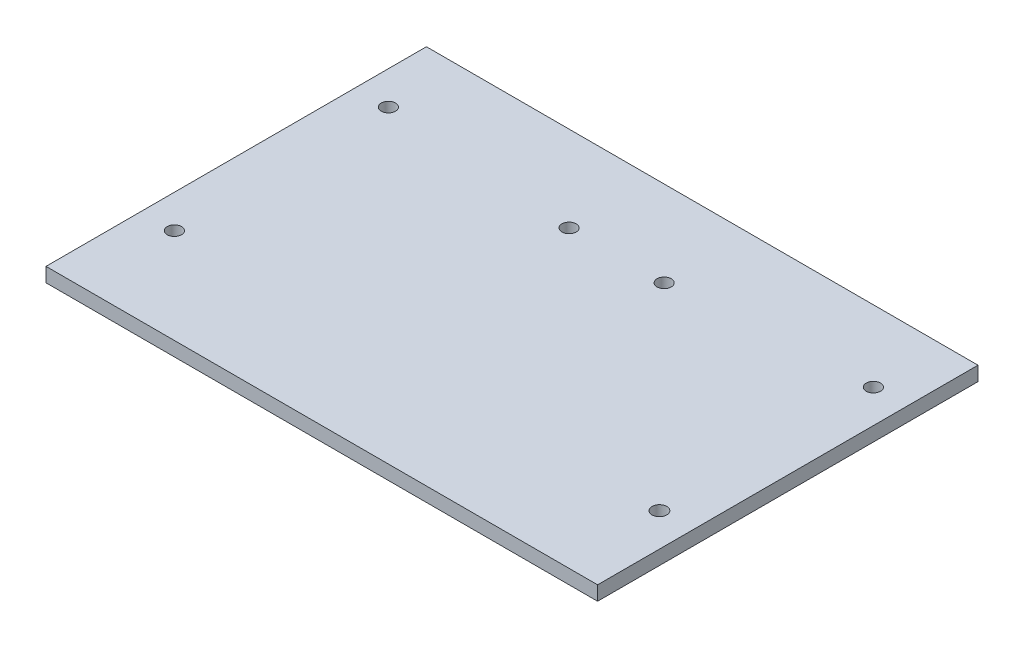
SolidWorks part; units mm, degrees
ref_plane "前视基准面" through (0, 0, 0) normal (0, 0, 1) x (1, 0, 0)
ref_plane "上视基准面" through (0, 0, 0) normal (0, 1, 0) x (1, 0, 0)
ref_plane "右视基准面" through (0, 0, 0) normal (1, 0, 0) x (0, 0, -1)
other "Configuration Table"
sketch "草图1" plane through (0, 0, 0) normal (0, 1, 0) x (1, 0, 0)
  line L1 (58, -40) -> (-58, -40)
  line L2 (58, -40) -> (58, 40)
  line L3 (58, 40) -> (-58, 40)
  line L4 (-58, -40) -> (-58, 40)
  line L5 (58, -40) -> (-58, 40) construction
  line L6 (58, 40) -> (-58, -40) construction
  point P0 (0, 0)
  dimension "D1" = 116
  dimension "D2" = 80
extrude "凸台-拉伸1" add sketch "草图1" along normal blind 3
sketch "草图2" plane through (0, 0, 0) normal (0, -1, 0) x (1, 0, 0)
  line L0 (-58, 40) -> (58, 40) construction
  line L1 (-58, -40) -> (-58, 40) construction
  line L2 (58, 40) -> (58, -40) construction
  line L3 (58, -40) -> (-58, -40) construction
  circle A0 centre (-51, 20) radius 1.5
  circle A1 centre (51, 20) radius 1.55
  circle A2 centre (51, -25) radius 1.5
  circle A3 centre (-51, -25) radius 1.5
  dimension "D1" = 20
  dimension "D2" = 7
  dimension "D3" = 7
  dimension "D4" = 20
  dimension "D5" = 15
  dimension "D6" = 7
  dimension "D7" = 7
  dimension "D8" = 15
extrude "切除-拉伸1" cut sketch "草图2" against normal blind 10
sketch "草图3" plane through (0, 3, 0) normal (0, 1, 0) x (1, 0, 0)
  circle A0 centre (-10, 22) radius 1.5
  circle A1 centre (10, 22) radius 1.5
extrude "切除-拉伸2" cut sketch "草图3" against normal through all
